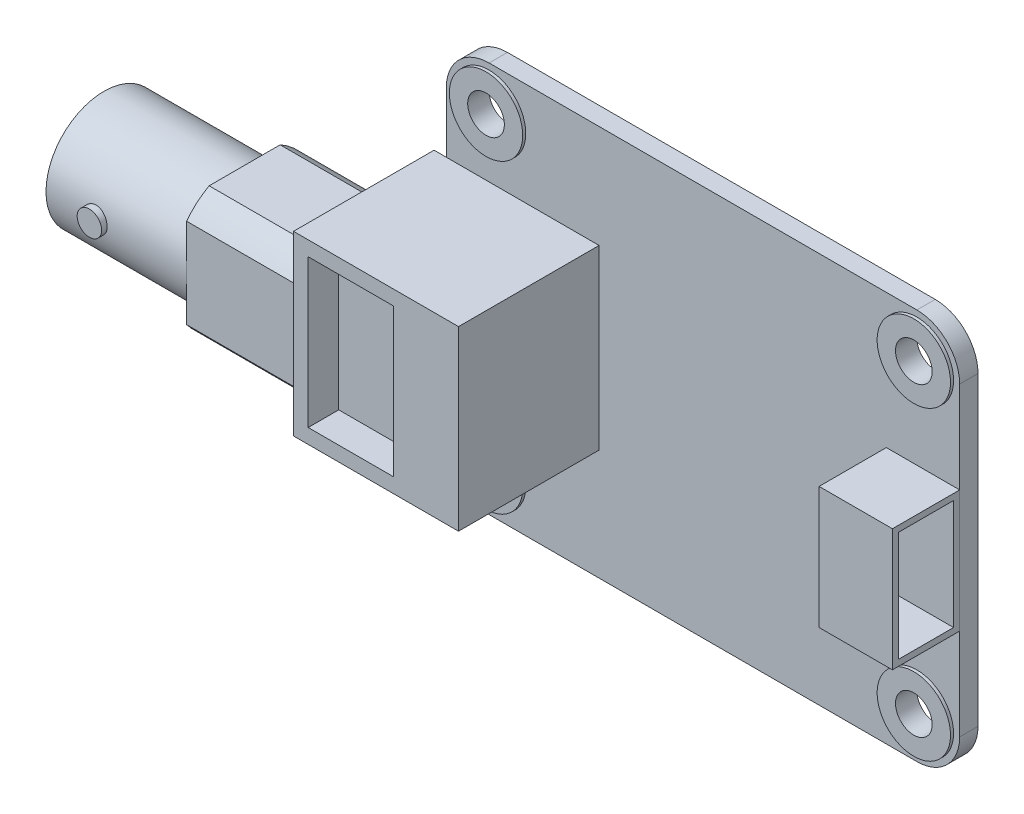
SolidWorks part; units mm, degrees
ref_plane "Plan de face" through (0, 0, 0) normal (0, 0, 1) x (1, 0, 0)
ref_plane "Plan de dessus" through (0, 0, 0) normal (0, 1, 0) x (1, 0, 0)
ref_plane "Plan de droite" through (0, 0, 0) normal (1, 0, 0) x (0, 0, -1)
sketch "Esquisse1" plane through (0, 0, 0) normal (0, 0, 1) x (1, 0, 0)
  line L1 (-17.5, -16) -> (17.5, -16)
  line L2 (-21, -12.5) -> (-21, 12.5)
  line L3 (-17.5, 16) -> (17.5, 16)
  line L4 (21, -12.5) -> (21, 12.5)
  line L5 (-21, -16) -> (21, 16) construction
  line L6 (-21, 16) -> (21, -16) construction
  arc A0 (17.5, 16) -> (21, 12.5) centre (17.5, 12.5) cw
  arc A1 (17.5, -16) -> (21, -12.5) centre (17.5, -12.5) ccw
  arc A2 (-17.5, -16) -> (-21, -12.5) centre (-17.5, -12.5) cw
  arc A3 (-21, 12.5) -> (-17.5, 16) centre (-17.5, 12.5) cw
  circle A4 centre (-17.5, 12.5) radius 1.5
  circle A5 centre (-17.5, -12.5) radius 1.5
  circle A6 centre (17.5, 12.5) radius 1.5
  circle A7 centre (17.5, -12.5) radius 1.5
  point P0 (0, 0)
  dimension "D3" = 3.5
  dimension "D4" = 3
  dimension "D1" = 42
  dimension "D2" = 32
extrude "Boss.-Extru.1" add sketch "Esquisse1" along normal blind 1.5 contours A3 L2 A2 L1 A1 L4 A0 L3 A7 A6 A5 A4 region at (0, 0, 0)
sketch "Esquisse2" plane through (0, 0, 1.5) normal (0, 0, 1) x (1, 0, 0)
  circle A0 centre (17.5, 12.5) radius 3
  circle A1 centre (-17.5, 12.5) radius 3
  circle A2 centre (-17.5, -12.5) radius 3
  circle A3 centre (17.5, -12.5) radius 3
  circle A4 centre (-17.5, -12.5) radius 1.5 construction
  circle A5 centre (17.5, -12.5) radius 1.5 construction
  circle A6 centre (17.5, 12.5) radius 1.5 construction
  circle A7 centre (-17.5, 12.5) radius 1.5 construction
  circle A8 centre (-17.5, -12.5) radius 1.5
  circle A9 centre (17.5, -12.5) radius 1.5
  circle A10 centre (17.5, 12.5) radius 1.5
  circle A11 centre (-17.5, 12.5) radius 1.5
  dimension "D1" = 6
extrude "Boss.-Extru.2" add sketch "Esquisse2" along normal blind 0.25
sketch "Esquisse4" plane through (0, 0, 1.5) normal (0, 0, 1) x (1, 0, 0)
  line L0 (-21, -12.5) -> (-21, 12.5) construction
  line L1 (-22, -6.928) -> (-8.5, -6.928)
  line L2 (-22, -6.928) -> (-22, 7.572)
  line L3 (-22, 7.572) -> (-8.5, 7.572)
  line L4 (-8.5, -6.928) -> (-8.5, 7.572)
  line L5 (-22, -6.928) -> (-8.5, 7.572) construction
  line L6 (-22, 7.572) -> (-8.5, -6.928) construction
  point P0 (-15.25, 0.322)
  dimension "D1" = 1
  dimension "D2" = 13.5
  dimension "D3" = 14.5
extrude "Boss.-Extru.3" add sketch "Esquisse4" along normal blind 11.5 separate body
sketch "Esquisse5" plane through (0, 0, 13) normal (0, 0, 1) x (1, 0, 0)
  line L0 (-8.5, 7.572) -> (-22, 7.572) construction
  line L1 (-20.8, 6.372) -> (-13.8, 6.372)
  line L2 (-20.8, 6.372) -> (-20.8, -5.728)
  line L3 (-20.8, -5.728) -> (-13.8, -5.728)
  line L4 (-13.8, 6.372) -> (-13.8, -5.728)
  line L5 (-22, 7.572) -> (-22, -6.928) construction
  line L6 (-22, -6.928) -> (-8.5, -6.928) construction
  dimension "D1" = 1.2
  dimension "D2" = 1.2
  dimension "D3" = 1.2
  dimension "D4" = 7
extrude "Enlèv. mat.-Extru.1" cut sketch "Esquisse5" against normal blind 2.5
sketch "Esquisse6" plane through (-22, 0, 0) normal (-1, 0, 0) x (0, 0, 1)
  line L0 (13, 7.572) -> (13, -6.928) construction
  circle A0 centre (8, 0) radius 6
  dimension "D1" = 12
  dimension "D2" = 5
extrude "Boss.-Extru.4" add sketch "Esquisse6" along normal blind 9
sketch "Esquisse7" plane through (-31, 0, 0) normal (-1, 0, 0) x (0, 0, 1)
  circle A0 centre (8, 0) radius 4.75
  circle A1 centre (8, 0) radius 4.15
  dimension "D1" = 9.5
  dimension "D2" = 8.3
extrude "Boss.-Extru.5" add sketch "Esquisse7" along normal blind 11.5
sketch "Esquisse8" plane through (-31, 0, 0) normal (-1, 0, 0) x (0, 0, 1)
  line L0 (13, 7.572) -> (13, 3.3166) construction
  line L1 (12.75, 5.25) -> (1.7838, 5.25)
  line L2 (12.75, 5.25) -> (12.75, -5.25)
  line L3 (12.75, -5.25) -> (1.7838, -5.25)
  line L4 (1.7838, 5.25) -> (1.7838, -5.25)
  point P6 (12.75, 0)
  dimension "D1" = 0.25
  dimension "D2" = 10.5
extrude "Enlèv. mat.-Extru.2" cut sketch "Esquisse8" against normal up to surface (9 mm away) flip side to cut up to face at (-22, 0.2147, 7.3333)
ref_plane "Plan1" through (0, 0, 13.2) normal (0, 0, 1) x (1, 0, 0)
sketch "Esquisse9" plane through (0, 0, 13.2) normal (0, 0, 1) x (1, 0, 0)
  line L0 (-42.5, 4.75) -> (-42.5, -4.75) construction
  circle A0 centre (-38.5, 0) radius 1
  dimension "D1" = 2
  dimension "D2" = 4
extrude "Boss.-Extru.6" add sketch "Esquisse9" against normal blind 1
extrude "Boss.-Extru.7" add sketch "Esquisse9<2>" along normal blind 1 from offset 10.5 offset against normal yes
sketch "Esquisse9<2>" plane through (0, 0, 13.2) normal (0, 0, 1) x (1, 0, 0) same geometry as "Esquisse9"
sketch "Esquisse10" plane through (-31, 0, 0) normal (-1, 0, 0) x (0, 0, 1)
  circle A0 centre (8, 0) radius 2
  circle A1 centre (8, 0) radius 0.75
  dimension "D1" = 4
  dimension "D2" = 1.5
extrude "Boss.-Extru.8" add sketch "Esquisse10" along normal blind 9
sketch "Esquisse11" plane through (0, 0, 1.5) normal (0, 0, 1) x (1, 0, 0)
  line L0 (21, -12.5) -> (21, 12.5) construction
  line L1 (21, 5) -> (15, 5)
  line L2 (21, 5) -> (21, -5)
  line L3 (21, -5) -> (15, -5)
  line L4 (15, 5) -> (15, -5)
  point P6 (15, 0)
  dimension "D1" = 10
  dimension "D2" = 6
extrude "Boss.-Extru.9" add sketch "Esquisse11" along normal blind 5.5 separate body
shell "Coque1" thickness 0.5 removed face at (21, 0, 4.25)
